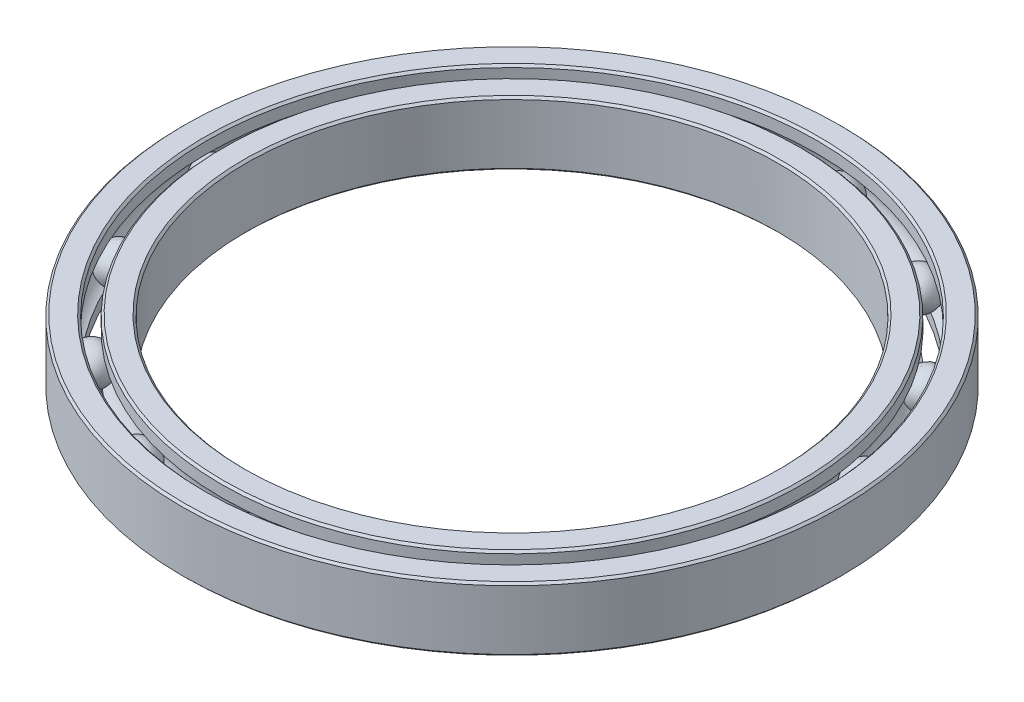
SolidWorks part; units mm, degrees
ref_plane "Front Plane" through (0, 0, 0) normal (0, 0, 1) x (1, 0, 0)
ref_plane "Top Plane" through (0, 0, 0) normal (0, 1, 0) x (1, 0, 0)
ref_plane "Right Plane" through (0, 0, 0) normal (1, 0, 0) x (0, 0, -1)
ref_axis "Axis1" through (0, 0, 0) along (0, 1, 0)
sketch "Sketch1" plane through (0, 0, 0) normal (0, 0, 1) x (1, 0, 0)
  line L0 (0, 0) -> (0, -9906.4977) construction
  line L1 (-28.6814, 0) -> (-31, 0)
  line L2 (-31, 0) -> (-31, 6)
  line L3 (-31, 6) -> (-28.6814, 6)
  line L4 (-28.6814, 6) -> (-28.6814, 4.7243)
  line L5 (-25, 5.2144) -> (-25, -49994.7856) construction
  line L6 (-28.6814, 1.2757) -> (-28.6814, 0)
  line L7 (-25, 0) -> (-27.3186, 0)
  line L8 (-25, 0) -> (-25, 6)
  line L9 (-25, 6) -> (-27.3186, 6)
  line L10 (-27.3186, 0) -> (-27.3186, 1.2757)
  line L11 (-27.3186, 4.7243) -> (-27.3186, 6)
  arc A0 (-28.6814, 4.7243) -> (-28.6814, 1.2757) centre (-28, 3) ccw
  arc A1 (-27.3186, 4.7243) -> (-27.3186, 1.2757) centre (-28, 3) cw
  point P15 (-26.9011, 4.6498)
  point P19 (0, 0)
  point P20 (0, 0)
  point P21 (0, 0)
  point P22 (-26.931, 1.2799)
  point P23 (0, 0)
  point P24 (-31, 3)
  point P25 (-27.3186, 4.7243)
  dimension "D1" = 62
  dimension "D2" = 6
  dimension "D3" = 25
revolve "Revolve1" add sketch "Sketch1" angle 360 about L0
chamfer "Chamfer1" distance 0.2 angle 45 4 edges at (0, 0, 25) (0, 6, 25) (0, 0, 27.3186) (0, 6, 27.3186)
chamfer "Chamfer2" distance 0.2 angle 45 4 edges at (0, 6, 31) (0, 0, 31) (0, 6, 28.6814) (0, 0, 28.6814)
sketch "Sketch2" plane through (0, 0, 0) normal (0, 0, 1) x (1, 0, 0)
  line L0 (-31, 3) -> (-25, 3) construction
  line L1 (-31, 0) -> (-31, 6) construction
  line L2 (-25, 0) -> (-25, 6) construction
  line L3 (-29.8236, 3) -> (-26.1764, 3)
  arc A0 (-29.8236, 3) -> (-26.1764, 3) centre (-28, 3) cw
  point P9 (-29.8236, 3)
  point P10 (-28, 3)
revolve "Revolve2" add sketch "Sketch2" angle 360 about L0
pattern_circular "CirPattern2" count 15 over 360 about axis through (0, 0, 0) along (0, 1, 0) of bodies 103
